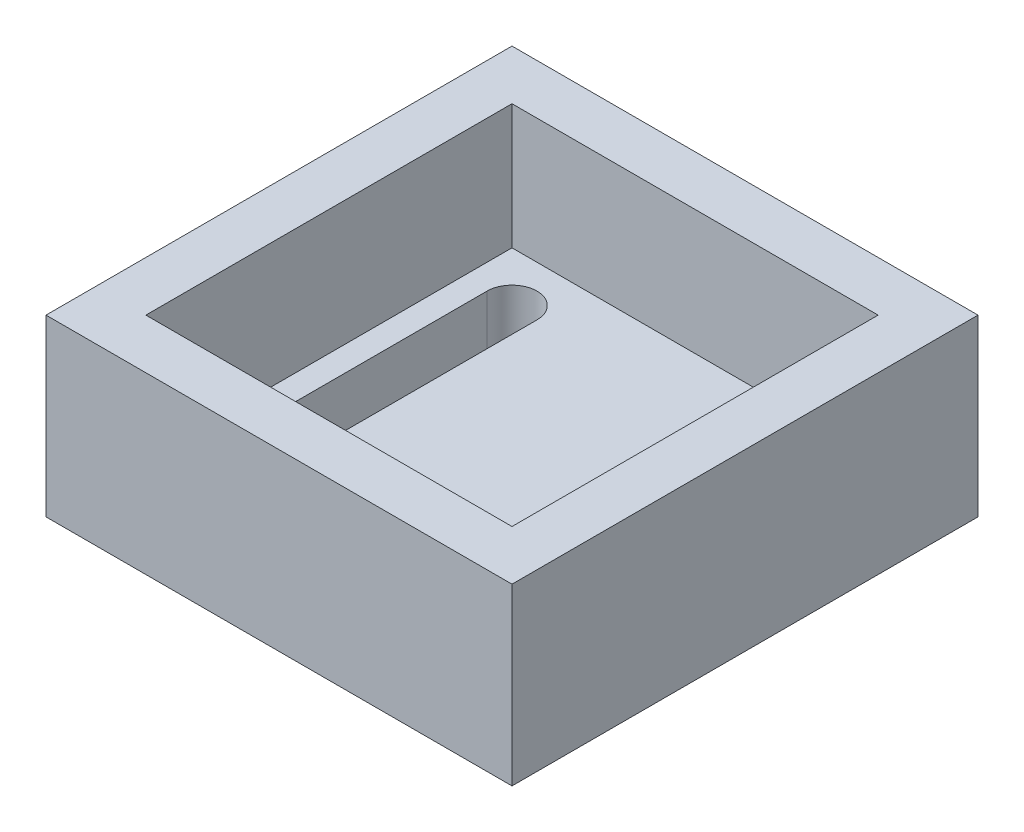
SolidWorks part; units mm, degrees
ref_plane "Front Plane" through (0, 0, 0) normal (0, 0, 1) x (1, 0, 0)
ref_plane "Top Plane" through (0, 0, 0) normal (0, 1, 0) x (1, 0, 0)
ref_plane "Right Plane" through (0, 0, 0) normal (1, 0, 0) x (0, 0, -1)
sketch "Sketch2" plane through (0, 0, 0) normal (0, 1, 0) x (1, 0, 0)
  line L1 (0, 0) -> (28, 0)
  line L2 (0, 0) -> (0, 28)
  line L3 (0, 28) -> (28, 28)
  line L4 (28, 0) -> (28, 28)
  dimension "D1" = 28
  dimension "D2" = 28
sketch "Sketch3" plane through (0, 0, 0) normal (0, 1, 0) x (1, 0, 0)
  line L0 (6, 22) -> (6, 6) construction
  line L1 (7.5, 22) -> (7.5, 6)
  line L2 (4.5, 22) -> (4.5, 6)
  circle A1 centre (22, 22) radius 1.5
  circle A2 centre (22, 6) radius 1.5
  arc A3 (7.5, 22) -> (4.5, 22) centre (6, 22) ccw
  arc A4 (4.5, 6) -> (7.5, 6) centre (6, 6) ccw
  point P9 (6, 14)
  dimension "D1" = 3
  dimension "D2" = 3
  dimension "D3" = 1.5
extrude "Boss-Extrude1" add sketch "Sketch2" along normal blind 10.5 contours L2 L1 L4 L3
extrude "Cut-Extrude1" cut sketch "Sketch3" along normal through all
sketch "Sketch5" plane through (0, 10.5, 0) normal (0, 1, 0) x (1, 0, 0)
  line L5 (3, 25) -> (25, 25)
  line L6 (3, 25) -> (3, 3)
  line L7 (3, 3) -> (25, 3)
  line L8 (25, 25) -> (25, 3)
  line L9 (3, 25) -> (25, 3) construction
  line L10 (3, 3) -> (25, 25) construction
  point P0 (14, 14)
  dimension "D1" = 22
  dimension "D2" = 22
extrude "Cut-Extrude2" cut sketch "Sketch5" against normal blind 7.5
